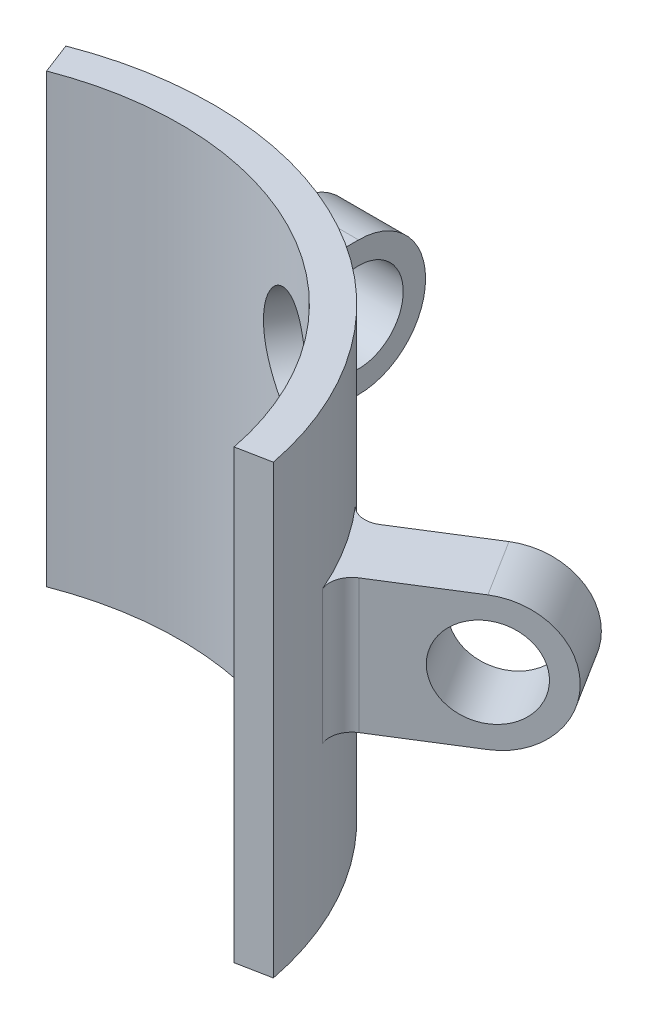
SolidWorks part; units mm, degrees
material "1060 Alloy"
ref_plane "Front Plane" through (0, 0, 0) normal (0, 0, 1) x (1, 0, 0)
ref_plane "Top Plane" through (0, 0, 0) normal (0, 1, 0) x (1, 0, 0)
ref_plane "Right Plane" through (0, 0, 0) normal (1, 0, 0) x (0, 0, -1)
sketch "Sketch2" plane through (0, 0, 0) normal (0, 1, 0) x (1, 0, 0)
  circle A0 centre (0, 0) radius 14
  circle A1 centre (0, 0) radius 15.5
  dimension "D1" = 28
  dimension "D2" = 1.5
extrude "Boss-Extrude1" add sketch "Sketch2" along normal blind 20
sketch "Sketch3" plane through (0, 20, 0) normal (0, 1, 0) x (1, 0, 0)
  line L0 (0, 0) -> (7.5, 13.5647)
  line L1 (0, 0) -> (-7.5, 13.5647)
  line L2 (7.5, 13.5647) -> (-7.5, 13.5647) construction
  circle A0 centre (0, 0) radius 15.5 construction
  arc A1 (7.5, 13.5647) -> (-7.5, 13.5647) centre (0, 0) ccw
  point P6 (0, 15.5)
  dimension "D1" = 15
extrude "Cut-Extrude1" cut sketch "Sketch3" against normal through all flip side to cut
ref_plane "Plane1" through (0, 10, 0) normal (0, 1, 0) x (1, 0, 0)
sketch "Sketch6" plane through (0, 7.5, 0) normal (-1, 0, 0) x (0, 1, 0)
  line L0 (-0.5, 20.5) -> (-0.5, 15.25)
  line L1 (5.5, 20.5) -> (5.5, 15.25)
  line L2 (12.5, 15.5) -> (-7.5, 15.5) construction
  line L3 (12.5, 12.252) -> (-7.5, 12.252) construction
  line L4 (-0.5, 15.25) -> (5.5, 15.25)
  line L5 (12.5, 15.5) -> (-7.5, 15.5) construction
  circle A0 centre (2.5, 20.5) radius 2
  arc A1 (5.5, 20.5) -> (-0.5, 20.5) centre (2.5, 20.5) ccw
  point P10 (2.5, 12.252)
  dimension "D1" = 4
  dimension "D2" = 1
  dimension "D4" = 5
  dimension "D3" = 0.25
extrude "Boss-Extrude2" add sketch "Sketch6" along normal blind 1.5 and the other way blind 1.5
mirror "Mirror2" about plane through (0, 0, 0) normal (0.8751, 0, 0.4839) of "Boss-Extrude2", "Boss-Extrude1"
sketch "Sketch8" plane through (0, 0, 0) normal (0, 1, 0) x (1, 0, 0)
  line L0 (-5.5702, 14.4645) -> (0, 0)
  line L1 (0, 0) -> (15.212, 2.9739)
  line L2 (-5.5702, 14.4645) -> (-1.5, 23.5) construction
  line L3 (0, 15.5) -> (-5.5702, 14.4645) construction
  line L4 (20.7, 11.2255) -> (15.212, 2.9739) construction
  line L5 (13.1271, 8.2419) -> (15.212, 2.9739) construction
  arc A0 (-5.5702, 14.4645) -> (15.212, 2.9739) centre (0, 0) ccw
  circle A1 centre (0, 0) radius 15.5 construction
  arc A2 (1.5, 15.4272) -> (-1.5, 15.4272) centre (0, 0) ccw construction
  arc A3 (13.8631, 6.9329) -> (12.2679, 9.4736) centre (0, 0) ccw construction
  dimension "D1" = 100
extrude "Cut-Extrude4" cut sketch "Sketch8" against normal blind 10 and the other way through all contours L1 A0 L0
ref_plane "Plane2" through (4.3544, 0, -7.8754) normal (0.4839, 0, -0.8751) x (-0.8751, 0, -0.4839)
sketch "Sketch9" plane through (4.3544, 0, -7.8754) normal (0.4839, 0, -0.8751) x (-0.8751, 0, -0.4839)
  line L0 (0, 15) -> (0, 20) construction
  line L1 (11.8737, 20) -> (-11.8737, 20) construction
  line L2 (0, 5) -> (0, 0) construction
  circle A0 centre (0, 15) radius 2.5
  circle A1 centre (0, 5) radius 2.5
  dimension "D1" = 5
  dimension "D2" = 5
extrude "Cut-Extrude5" cut sketch "Sketch9" along normal blind 10
fillet "Fillet1" radius 1 4 edges at (13.8631, 10, -6.9329) (-1.5, 10, -15.4272) (1.5, 10, -15.4272) (12.2679, 10, -9.4736)
equation "\"keelOutDiameter\"= 1in"
equation "\"poleOutDiameter\"= 28mm"
equation "\"poleLength\"=650mm"
equation "\"propellerTubeOutDiameter\"= 28mm"
equation "\"propellerDiameter\"= 700mm"
equation "\"D1@Sketch2\"=\"poleOutDiameter\""
